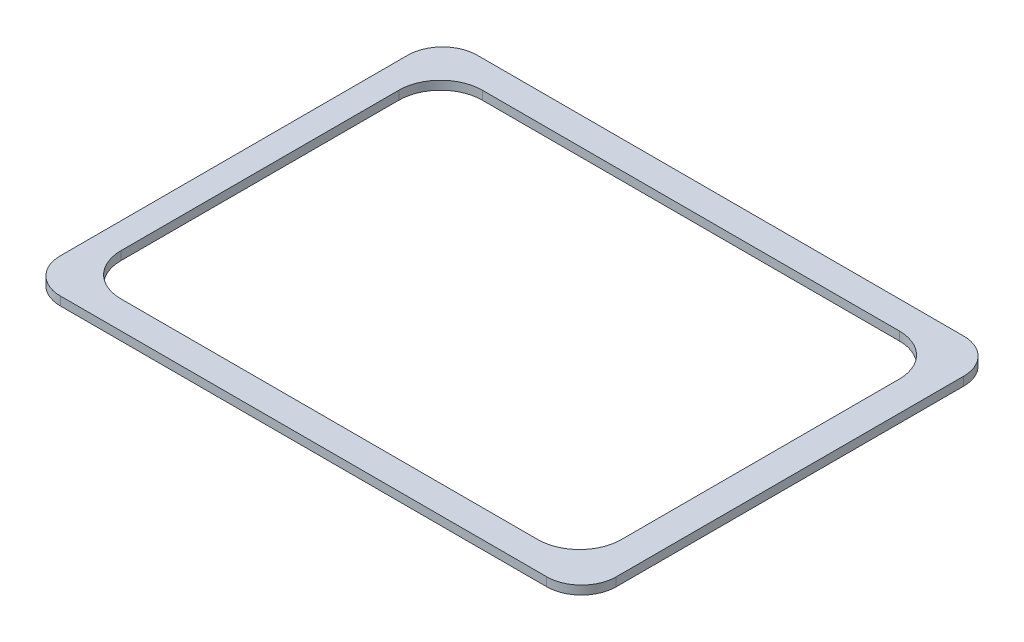
SolidWorks part; units mm, degrees
ref_plane "Front Plane" through (0, 0, 0) normal (0, 0, 1) x (1, 0, 0)
ref_plane "Top Plane" through (0, 0, 0) normal (0, 1, 0) x (1, 0, 0)
ref_plane "Right Plane" through (0, 0, 0) normal (1, 0, 0) x (0, 0, -1)
ref_plane "MaskPlane" through (0, 7.5248, 0) normal (0, 1, 0) x (1, 0, 0)
sketch "Sketch1" plane through (0, 7.5248, 0) normal (0, 1, 0) x (-1, 0, 0)
  line L19 (-90.75, 50.8) -> (-90.75, 0)
  line L25 (-90.75, 50.8) -> (-90.75, 0)
  line L27 (-90.75, 0) -> (-90.75, -50.8)
  line L44 (-101.6, 63.5) -> (-101.6, -63.5) construction
  line L45 (-88.9, -76.2) -> (88.9, -76.2) construction
  line L46 (101.6, -63.5) -> (101.6, 63.5) construction
  line L47 (88.9, 76.2) -> (-88.9, 76.2) construction
  line L52 (-101.6, 63.5) -> (-101.6, -63.5)
  line L53 (-88.9, -76.2) -> (88.9, -76.2)
  line L54 (101.6, -63.5) -> (101.6, 63.5)
  line L55 (88.9, 76.2) -> (-88.9, 76.2)
  line L168 (-90.75, 0) -> (-90.75, -50.8)
  line L176 (-75.5, -66.05) -> (76.9, -66.05)
  line L177 (-75.5, -66.05) -> (76.9, -66.05)
  line L178 (92.15, -50.8) -> (92.15, 50.8)
  line L179 (92.15, -50.8) -> (92.15, 50.8)
  line L180 (76.9, 66.05) -> (-75.5, 66.05)
  line L181 (76.9, 66.05) -> (-75.5, 66.05)
  arc A4 (-88.9, 76.2) -> (-101.6, 63.5) centre (-88.9, 63.5) ccw construction
  arc A6 (-101.6, -63.5) -> (-88.9, -76.2) centre (-88.9, -63.5) ccw construction
  arc A8 (88.9, -76.2) -> (101.6, -63.5) centre (88.9, -63.5) ccw construction
  arc A10 (101.6, 63.5) -> (88.9, 76.2) centre (88.9, 63.5) ccw construction
  arc A16 (-88.9, 76.2) -> (-101.6, 63.5) centre (-88.9, 63.5) ccw
  arc A17 (-101.6, -63.5) -> (-88.9, -76.2) centre (-88.9, -63.5) ccw
  arc A18 (88.9, -76.2) -> (101.6, -63.5) centre (88.9, -63.5) ccw
  arc A19 (101.6, 63.5) -> (88.9, 76.2) centre (88.9, 63.5) ccw
  arc A24 (-90.75, -50.8) -> (-75.5, -66.05) centre (-75.5, -50.8) ccw
  arc A26 (-90.75, -50.8) -> (-75.5, -66.05) centre (-75.5, -50.8) ccw
  arc A132 (76.9, -66.05) -> (92.15, -50.8) centre (76.9, -50.8) ccw
  arc A134 (76.9, -66.05) -> (92.15, -50.8) centre (76.9, -50.8) ccw
  arc A140 (92.15, 50.8) -> (76.9, 66.05) centre (76.9, 50.8) ccw
  arc A141 (92.15, 50.8) -> (76.9, 66.05) centre (76.9, 50.8) ccw
  arc A142 (-75.5, 66.05) -> (-90.75, 50.8) centre (-75.5, 50.8) ccw
  arc A143 (-75.5, 66.05) -> (-90.75, 50.8) centre (-75.5, 50.8) ccw
  dimension "D1" = 3
extrude "FrontFace" add sketch "Sketch1" along normal blind 3.175
sketch "Sketch2" [suppressed] plane through (0, 10.3187, 0) normal (0, 1, 0) x (1, 0, 0)
  line L1 (-98.6155, 53.975) -> (-95.4405, 53.975)
  line L2 (-98.6155, 53.975) -> (-98.6155, -53.975)
  line L3 (-98.6155, -53.975) -> (-95.4405, -53.975)
  line L4 (-95.4405, 53.975) -> (-95.4405, -53.975)
  line L5 (-73.025, -70.0405) -> (73.025, -70.0405)
  line L6 (-73.025, -70.0405) -> (-73.025, -73.2155)
  line L7 (-73.025, -73.2155) -> (73.025, -73.2155)
  line L8 (73.025, -70.0405) -> (73.025, -73.2155)
  line L9 (95.4405, -53.975) -> (98.6155, -53.975)
  line L10 (95.4405, -53.975) -> (95.4405, 53.975)
  line L11 (95.4405, 53.975) -> (98.6155, 53.975)
  line L12 (98.6155, -53.975) -> (98.6155, 53.975)
  line L13 (73.025, 73.2155) -> (-73.025, 73.2155)
  line L14 (73.025, 73.2155) -> (73.025, 70.0405)
  line L15 (73.025, 70.0405) -> (-73.025, 70.0405)
  line L16 (-73.025, 73.2155) -> (-73.025, 70.0405)
  line L132 (95.25, -53.975) -> (101.6, -53.975)
  line L133 (95.25, -60.325) -> (95.25, -53.975)
  line L134 (101.6, -60.325) -> (95.25, -60.325)
  line L135 (101.6, -63.5) -> (101.6, -60.325)
  line L136 (79.375, -76.2) -> (88.9, -76.2)
  line L137 (79.375, -69.85) -> (79.375, -76.2)
  line L138 (73.025, -69.85) -> (79.375, -69.85)
  line L139 (73.025, -76.2) -> (73.025, -69.85)
  line L140 (60.325, -76.2) -> (73.025, -76.2)
  line L141 (60.325, -69.85) -> (60.325, -76.2)
  line L142 (53.975, -69.85) -> (60.325, -69.85)
  line L143 (53.975, -76.2) -> (53.975, -69.85)
  line L144 (41.275, -76.2) -> (53.975, -76.2)
  line L145 (41.275, -69.85) -> (41.275, -76.2)
  line L146 (34.925, -69.85) -> (41.275, -69.85)
  line L147 (34.925, -76.2) -> (34.925, -69.85)
  line L148 (22.225, -76.2) -> (34.925, -76.2)
  line L149 (22.225, -69.85) -> (22.225, -76.2)
  line L150 (15.875, -69.85) -> (22.225, -69.85)
  line L151 (15.875, -76.2) -> (15.875, -69.85)
  line L152 (3.175, -76.2) -> (15.875, -76.2)
  line L153 (3.175, -69.85) -> (3.175, -76.2)
  line L154 (-3.175, -69.85) -> (3.175, -69.85)
  line L155 (-3.175, -76.2) -> (-3.175, -69.85)
  line L156 (-15.875, -76.2) -> (-3.175, -76.2)
  line L157 (-15.875, -69.85) -> (-15.875, -76.2)
  line L158 (-22.225, -69.85) -> (-15.875, -69.85)
  line L159 (-22.225, -76.2) -> (-22.225, -69.85)
  line L160 (-34.925, -76.2) -> (-22.225, -76.2)
  line L161 (-34.925, -69.85) -> (-34.925, -76.2)
  line L162 (-41.275, -69.85) -> (-34.925, -69.85)
  line L163 (-41.275, -76.2) -> (-41.275, -69.85)
  line L164 (-53.975, -76.2) -> (-41.275, -76.2)
  line L165 (-53.975, -69.85) -> (-53.975, -76.2)
  line L166 (-60.325, -69.85) -> (-53.975, -69.85)
  line L167 (-60.325, -76.2) -> (-60.325, -69.85)
  line L168 (-73.025, -76.2) -> (-60.325, -76.2)
  line L169 (-73.025, -69.85) -> (-73.025, -76.2)
  line L170 (-79.375, -69.85) -> (-73.025, -69.85)
  line L171 (-79.375, -76.2) -> (-79.375, -69.85)
  line L172 (-88.9, -76.2) -> (-79.375, -76.2)
  line L173 (-101.6, -60.325) -> (-101.6, -63.5)
  line L174 (-95.25, -60.325) -> (-101.6, -60.325)
  line L175 (-95.25, -53.975) -> (-95.25, -60.325)
  line L176 (-101.6, -53.975) -> (-95.25, -53.975)
  line L177 (-101.6, -41.275) -> (-101.6, -53.975)
  line L178 (-95.25, -41.275) -> (-101.6, -41.275)
  line L179 (-95.25, -34.925) -> (-95.25, -41.275)
  line L180 (-101.6, -34.925) -> (-95.25, -34.925)
  line L181 (-101.6, -22.225) -> (-101.6, -34.925)
  line L182 (-95.25, -22.225) -> (-101.6, -22.225)
  line L183 (-95.25, -15.875) -> (-95.25, -22.225)
  line L184 (-101.6, -15.875) -> (-95.25, -15.875)
  line L185 (-101.6, -3.175) -> (-101.6, -15.875)
  line L186 (-95.25, -3.175) -> (-101.6, -3.175)
  line L187 (-95.25, 3.175) -> (-95.25, -3.175)
  line L188 (-101.6, 3.175) -> (-95.25, 3.175)
  line L189 (-101.6, 15.875) -> (-101.6, 3.175)
  line L190 (-95.25, 15.875) -> (-101.6, 15.875)
  line L191 (-95.25, 22.225) -> (-95.25, 15.875)
  line L192 (-101.6, 22.225) -> (-95.25, 22.225)
  line L193 (-101.6, 34.925) -> (-101.6, 22.225)
  line L194 (-95.25, 34.925) -> (-101.6, 34.925)
  line L195 (-95.25, 41.275) -> (-95.25, 34.925)
  line L196 (-101.6, 41.275) -> (-95.25, 41.275)
  line L197 (-101.6, 53.975) -> (-101.6, 41.275)
  line L198 (-95.25, 53.975) -> (-101.6, 53.975)
  line L199 (-95.25, 60.325) -> (-95.25, 53.975)
  line L200 (-101.6, 60.325) -> (-95.25, 60.325)
  line L201 (-101.6, 63.5) -> (-101.6, 60.325)
  line L202 (-79.375, 76.2) -> (-88.9, 76.2)
  line L203 (-79.375, 69.85) -> (-79.375, 76.2)
  line L204 (-73.025, 69.85) -> (-79.375, 69.85)
  line L205 (-73.025, 76.2) -> (-73.025, 69.85)
  line L206 (-60.325, 76.2) -> (-73.025, 76.2)
  line L207 (-60.325, 69.85) -> (-60.325, 76.2)
  line L208 (-53.975, 69.85) -> (-60.325, 69.85)
  line L209 (-53.975, 76.2) -> (-53.975, 69.85)
  line L210 (-41.275, 76.2) -> (-53.975, 76.2)
  line L211 (-41.275, 69.85) -> (-41.275, 76.2)
  line L212 (-34.925, 69.85) -> (-41.275, 69.85)
  line L213 (-34.925, 76.2) -> (-34.925, 69.85)
  line L214 (-22.225, 76.2) -> (-34.925, 76.2)
  line L215 (-22.225, 69.85) -> (-22.225, 76.2)
  line L216 (-15.875, 69.85) -> (-22.225, 69.85)
  line L217 (-15.875, 76.2) -> (-15.875, 69.85)
  line L218 (-3.175, 76.2) -> (-15.875, 76.2)
  line L219 (-3.175, 69.85) -> (-3.175, 76.2)
  line L220 (3.175, 69.85) -> (-3.175, 69.85)
  line L221 (3.175, 76.2) -> (3.175, 69.85)
  line L222 (15.875, 76.2) -> (3.175, 76.2)
  line L223 (15.875, 69.85) -> (15.875, 76.2)
  line L224 (22.225, 69.85) -> (15.875, 69.85)
  line L225 (22.225, 76.2) -> (22.225, 69.85)
  line L226 (34.925, 76.2) -> (22.225, 76.2)
  line L227 (34.925, 69.85) -> (34.925, 76.2)
  line L228 (41.275, 69.85) -> (34.925, 69.85)
  line L229 (41.275, 76.2) -> (41.275, 69.85)
  line L230 (53.975, 76.2) -> (41.275, 76.2)
  line L231 (53.975, 69.85) -> (53.975, 76.2)
  line L232 (60.325, 69.85) -> (53.975, 69.85)
  line L233 (60.325, 76.2) -> (60.325, 69.85)
  line L234 (73.025, 76.2) -> (60.325, 76.2)
  line L235 (73.025, 69.85) -> (73.025, 76.2)
  line L236 (79.375, 69.85) -> (73.025, 69.85)
  line L237 (79.375, 76.2) -> (79.375, 69.85)
  line L238 (88.9, 76.2) -> (79.375, 76.2)
  line L239 (101.6, 60.325) -> (101.6, 63.5)
  line L240 (95.25, 60.325) -> (101.6, 60.325)
  line L241 (95.25, 53.975) -> (95.25, 60.325)
  line L242 (101.6, 53.975) -> (95.25, 53.975)
  line L243 (101.6, 41.275) -> (101.6, 53.975)
  line L244 (95.25, 41.275) -> (101.6, 41.275)
  line L245 (95.25, 34.925) -> (95.25, 41.275)
  line L246 (101.6, 34.925) -> (95.25, 34.925)
  line L247 (101.6, 22.225) -> (101.6, 34.925)
  line L248 (95.25, 22.225) -> (101.6, 22.225)
  line L249 (95.25, 15.875) -> (95.25, 22.225)
  line L250 (101.6, 15.875) -> (95.25, 15.875)
  line L251 (101.6, 3.175) -> (101.6, 15.875)
  line L252 (95.25, 3.175) -> (101.6, 3.175)
  line L253 (95.25, -3.175) -> (95.25, 3.175)
  line L254 (101.6, -3.175) -> (95.25, -3.175)
  line L255 (101.6, -15.875) -> (101.6, -3.175)
  line L256 (95.25, -15.875) -> (101.6, -15.875)
  line L257 (95.25, -22.225) -> (95.25, -15.875)
  line L258 (101.6, -22.225) -> (95.25, -22.225)
  line L259 (101.6, -34.925) -> (101.6, -22.225)
  line L260 (95.25, -34.925) -> (101.6, -34.925)
  line L261 (95.25, -41.275) -> (95.25, -34.925)
  line L262 (101.6, -41.275) -> (95.25, -41.275)
  line L263 (101.6, -53.975) -> (101.6, -41.275)
  line L264 (95.25, -53.975) -> (101.6, -53.975)
  line L265 (95.25, -60.325) -> (95.25, -53.975)
  line L266 (101.6, -60.325) -> (95.25, -60.325)
  line L267 (101.6, -63.5) -> (101.6, -60.325)
  line L268 (79.375, -76.2) -> (88.9, -76.2)
  line L269 (79.375, -69.85) -> (79.375, -76.2)
  line L270 (73.025, -69.85) -> (79.375, -69.85)
  line L271 (73.025, -76.2) -> (73.025, -69.85)
  line L272 (60.325, -76.2) -> (73.025, -76.2)
  line L273 (60.325, -69.85) -> (60.325, -76.2)
  line L274 (53.975, -69.85) -> (60.325, -69.85)
  line L275 (53.975, -76.2) -> (53.975, -69.85)
  line L276 (41.275, -76.2) -> (53.975, -76.2)
  line L277 (41.275, -69.85) -> (41.275, -76.2)
  line L278 (34.925, -69.85) -> (41.275, -69.85)
  line L279 (34.925, -76.2) -> (34.925, -69.85)
  line L280 (22.225, -76.2) -> (34.925, -76.2)
  line L281 (22.225, -69.85) -> (22.225, -76.2)
  line L282 (15.875, -69.85) -> (22.225, -69.85)
  line L283 (15.875, -76.2) -> (15.875, -69.85)
  line L284 (3.175, -76.2) -> (15.875, -76.2)
  line L285 (3.175, -69.85) -> (3.175, -76.2)
  line L286 (-3.175, -69.85) -> (3.175, -69.85)
  line L287 (-3.175, -76.2) -> (-3.175, -69.85)
  line L288 (-15.875, -76.2) -> (-3.175, -76.2)
  line L289 (-15.875, -69.85) -> (-15.875, -76.2)
  line L290 (-22.225, -69.85) -> (-15.875, -69.85)
  line L291 (-22.225, -76.2) -> (-22.225, -69.85)
  line L292 (-34.925, -76.2) -> (-22.225, -76.2)
  line L293 (-34.925, -69.85) -> (-34.925, -76.2)
  line L294 (-41.275, -69.85) -> (-34.925, -69.85)
  line L295 (-41.275, -76.2) -> (-41.275, -69.85)
  line L296 (-53.975, -76.2) -> (-41.275, -76.2)
  line L297 (-53.975, -69.85) -> (-53.975, -76.2)
  line L298 (-60.325, -69.85) -> (-53.975, -69.85)
  line L299 (-60.325, -76.2) -> (-60.325, -69.85)
  line L300 (-73.025, -76.2) -> (-60.325, -76.2)
  line L301 (-73.025, -69.85) -> (-73.025, -76.2)
  line L302 (-79.375, -69.85) -> (-73.025, -69.85)
  line L303 (-79.375, -76.2) -> (-79.375, -69.85)
  line L304 (-88.9, -76.2) -> (-79.375, -76.2)
  line L305 (-101.6, -60.325) -> (-101.6, -63.5)
  line L306 (-95.25, -60.325) -> (-101.6, -60.325)
  line L307 (-95.25, -53.975) -> (-95.25, -60.325)
  line L308 (-101.6, -53.975) -> (-95.25, -53.975)
  line L309 (-101.6, -41.275) -> (-101.6, -53.975)
  line L310 (-95.25, -41.275) -> (-101.6, -41.275)
  line L311 (-95.25, -34.925) -> (-95.25, -41.275)
  line L312 (-101.6, -34.925) -> (-95.25, -34.925)
  line L313 (-101.6, -22.225) -> (-101.6, -34.925)
  line L314 (-95.25, -22.225) -> (-101.6, -22.225)
  line L315 (-95.25, -15.875) -> (-95.25, -22.225)
  line L316 (-101.6, -15.875) -> (-95.25, -15.875)
  line L317 (-101.6, -3.175) -> (-101.6, -15.875)
  line L318 (-95.25, -3.175) -> (-101.6, -3.175)
  line L319 (-95.25, 3.175) -> (-95.25, -3.175)
  line L320 (-101.6, 3.175) -> (-95.25, 3.175)
  line L321 (-101.6, 15.875) -> (-101.6, 3.175)
  line L322 (-95.25, 15.875) -> (-101.6, 15.875)
  line L323 (-95.25, 22.225) -> (-95.25, 15.875)
  line L324 (-101.6, 22.225) -> (-95.25, 22.225)
  line L325 (-101.6, 34.925) -> (-101.6, 22.225)
  line L326 (-95.25, 34.925) -> (-101.6, 34.925)
  line L327 (-95.25, 41.275) -> (-95.25, 34.925)
  line L328 (-101.6, 41.275) -> (-95.25, 41.275)
  line L329 (-101.6, 53.975) -> (-101.6, 41.275)
  line L330 (-95.25, 53.975) -> (-101.6, 53.975)
  line L331 (-95.25, 60.325) -> (-95.25, 53.975)
  line L332 (-101.6, 60.325) -> (-95.25, 60.325)
  line L333 (-101.6, 63.5) -> (-101.6, 60.325)
  line L334 (-79.375, 76.2) -> (-88.9, 76.2)
  line L335 (-79.375, 69.85) -> (-79.375, 76.2)
  line L336 (-73.025, 69.85) -> (-79.375, 69.85)
  line L337 (-73.025, 76.2) -> (-73.025, 69.85)
  line L338 (-60.325, 76.2) -> (-73.025, 76.2)
  line L339 (-60.325, 69.85) -> (-60.325, 76.2)
  line L340 (-53.975, 69.85) -> (-60.325, 69.85)
  line L341 (-53.975, 76.2) -> (-53.975, 69.85)
  line L342 (-41.275, 76.2) -> (-53.975, 76.2)
  line L343 (-41.275, 69.85) -> (-41.275, 76.2)
  line L344 (-34.925, 69.85) -> (-41.275, 69.85)
  line L345 (-34.925, 76.2) -> (-34.925, 69.85)
  line L346 (-22.225, 76.2) -> (-34.925, 76.2)
  line L347 (-22.225, 69.85) -> (-22.225, 76.2)
  line L348 (-15.875, 69.85) -> (-22.225, 69.85)
  line L349 (-15.875, 76.2) -> (-15.875, 69.85)
  line L350 (-3.175, 76.2) -> (-15.875, 76.2)
  line L351 (-3.175, 69.85) -> (-3.175, 76.2)
  line L352 (3.175, 69.85) -> (-3.175, 69.85)
  line L353 (3.175, 76.2) -> (3.175, 69.85)
  line L354 (15.875, 76.2) -> (3.175, 76.2)
  line L355 (15.875, 69.85) -> (15.875, 76.2)
  line L356 (22.225, 69.85) -> (15.875, 69.85)
  line L357 (22.225, 76.2) -> (22.225, 69.85)
  line L358 (34.925, 76.2) -> (22.225, 76.2)
  line L359 (34.925, 69.85) -> (34.925, 76.2)
  line L360 (41.275, 69.85) -> (34.925, 69.85)
  line L361 (41.275, 76.2) -> (41.275, 69.85)
  line L362 (53.975, 76.2) -> (41.275, 76.2)
  line L363 (53.975, 69.85) -> (53.975, 76.2)
  line L364 (60.325, 69.85) -> (53.975, 69.85)
  line L365 (60.325, 76.2) -> (60.325, 69.85)
  line L366 (73.025, 76.2) -> (60.325, 76.2)
  line L367 (73.025, 69.85) -> (73.025, 76.2)
  line L368 (79.375, 69.85) -> (73.025, 69.85)
  line L369 (79.375, 76.2) -> (79.375, 69.85)
  line L370 (88.9, 76.2) -> (79.375, 76.2)
  line L371 (101.6, 60.325) -> (101.6, 63.5)
  line L372 (95.25, 60.325) -> (101.6, 60.325)
  line L373 (95.25, 53.975) -> (95.25, 60.325)
  line L374 (101.6, 53.975) -> (95.25, 53.975)
  line L375 (101.6, 41.275) -> (101.6, 53.975)
  line L376 (95.25, 41.275) -> (101.6, 41.275)
  line L377 (95.25, 34.925) -> (95.25, 41.275)
  line L378 (101.6, 34.925) -> (95.25, 34.925)
  line L379 (101.6, 22.225) -> (101.6, 34.925)
  line L380 (95.25, 22.225) -> (101.6, 22.225)
  line L381 (95.25, 15.875) -> (95.25, 22.225)
  line L382 (101.6, 15.875) -> (95.25, 15.875)
  line L383 (101.6, 3.175) -> (101.6, 15.875)
  line L384 (95.25, 3.175) -> (101.6, 3.175)
  line L385 (95.25, -3.175) -> (95.25, 3.175)
  line L386 (101.6, -3.175) -> (95.25, -3.175)
  line L387 (101.6, -15.875) -> (101.6, -3.175)
  line L388 (95.25, -15.875) -> (101.6, -15.875)
  line L389 (95.25, -22.225) -> (95.25, -15.875)
  line L390 (101.6, -22.225) -> (95.25, -22.225)
  line L391 (101.6, -34.925) -> (101.6, -22.225)
  line L392 (95.25, -34.925) -> (101.6, -34.925)
  line L393 (95.25, -41.275) -> (95.25, -34.925)
  line L394 (101.6, -41.275) -> (95.25, -41.275)
  line L395 (101.6, -53.975) -> (101.6, -41.275)
  arc A4 (88.9, -76.2) -> (101.6, -63.5) centre (88.9, -63.5) ccw
  arc A5 (-101.6, -63.5) -> (-88.9, -76.2) centre (-88.9, -63.5) ccw
  arc A6 (-88.9, 76.2) -> (-101.6, 63.5) centre (-88.9, 63.5) ccw
  arc A7 (101.6, 63.5) -> (88.9, 76.2) centre (88.9, 63.5) ccw
  arc A8 (88.9, -76.2) -> (101.6, -63.5) centre (88.9, -63.5) ccw
  arc A9 (-101.6, -63.5) -> (-88.9, -76.2) centre (-88.9, -63.5) ccw
  arc A10 (-88.9, 76.2) -> (-101.6, 63.5) centre (-88.9, 63.5) ccw
  arc A11 (101.6, 63.5) -> (88.9, 76.2) centre (88.9, 63.5) ccw
  dimension "D2" = 3.175
  dimension "D3" = 2.9845
  dimension "D4" = 3.175
  dimension "D5" = 2.9845
  dimension "D6" = 2.9845
  dimension "D7" = 3.175
  dimension "D8" = 2.9845
  dimension "D9" = 3.175
  dimension "D1" = 0
extrude "Cut-Extrude2" [suppressed] cut sketch "Sketch2" against normal up to surface (3.175 mm away) contours L2 L328 L4 L1 | L4 L326 L2 L324 | L4 L322 L2 L320 | L4 L318 L2 L316 | L4 L314 L2 L312 | L4 L310 L2 L3 | L7 L299 L5 L6 | L5 L297 L7 L295 | L5 L293 L7 L291 | L5 L289 L7 L287 | L5 L285 L7 L283 | L5 L281 L7 L279 | L5 L277 L7 L275 | L5 L273 L7 L8 | L12 L394 L10 L9 | L10 L392 L12 L390 | L10 L388 L12 L386 | L10 L384 L12 L382 | L10 L380 L12 L378 | L10 L376 L12 L11 | L13 L365 L15 L14 | L15 L363 L13 L361 | L15 L359 L13 L357 | L15 L355 L13 L353 | L15 L351 L13 L349 | L15 L347 L13 L345 | L15 L343 L13 L341 | L15 L339 L13 L16 up to face at (0, 7.5248, 0)
equation "\"ShellWallThickness\"=0.115"
equation "\"ShellOverlap\"=0.625"
